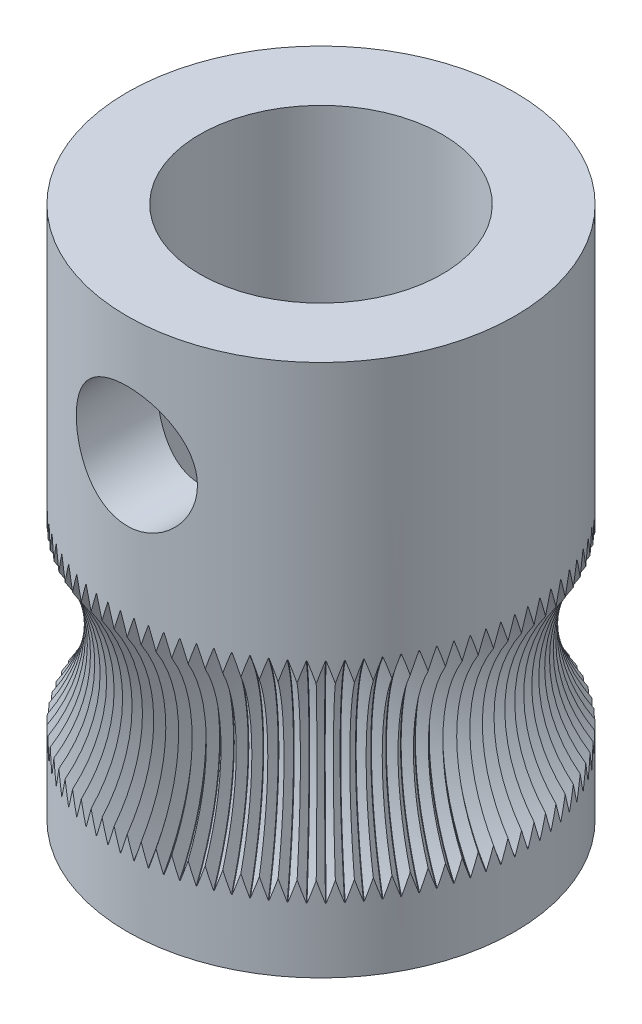
SolidWorks part; units mm, degrees
ref_plane "Front Plane" through (0, 0, 0) normal (0, 0, 1) x (1, 0, 0)
ref_plane "Top Plane" through (0, 0, 0) normal (0, 1, 0) x (1, 0, 0)
ref_plane "Right Plane" through (0, 0, 0) normal (1, 0, 0) x (0, 0, -1)
sketch "Sketch1" plane through (0, 0, 0) normal (0, 1, 0) x (1, 0, 0)
  circle A0 centre (0, 0) radius 4
  circle A1 centre (0, 0) radius 2.5
  dimension "D1" = 8
  dimension "D2" = 5
extrude "Boss-Extrude1" add sketch "Sketch1" along normal blind 11
ref_plane "Plane1" through (0, 0, 4) normal (0, 0, 1) x (1, 0, 0)
ref_axis "Axis1" through (0, 11, 0) along (0, -1, 0)
hole_wizard "M3 Tapped Hole1" positions "Sketch6" profile "Sketch7" tap size "M3" standard "ISO" end condition up to next
sketch "Sketch6" plane through (0, 0, 4) normal (0, 0, 1) x (1, 0, 0)
  line L0 (4, 11) -> (-4, 11) construction
  line L1 (0, 11) -> (0, 0) construction
  point P1 (0, 8.5)
  dimension "D1" = 2.5
cosmetic thread "Hole Thread1" parameters "D2"=3
sketch "Sketch7" plane through (0, 8.5, 4) normal (1, 0, 0) x (0, -1, 0)
  line L0 (0, 0) -> (0, 1.5)
  line L1 (0, 1.5) -> (1.25, 1.5)
  line L2 (1.25, 1.5) -> (1.25, 0)
  line L5 (1.25, 0) -> (0, 0)
  line L11 (0, -6.35) -> (0, 107.95) construction
  dimension "Thru Tap Drill Dia." = 2.5
  dimension "Thru Tap Drill Depth" = 1.5
ref_plane "Plane3" through (0, 0, 0) normal (0, 0, 1) x (1, 0, 0)
sketch "Sketch8" plane through (0, 0, 0) normal (0, 0, 1) x (1, 0, 0)
  line L0 (0, 11) -> (0, 0) construction
  line L1 (4, 11) -> (-4, 11) construction
  line L2 (6.75, 3.5) -> (6.75, 8.3641) construction
  circle A0 centre (6.75, 3.5) radius 3.5
  point P6 (6.75, 7)
  dimension "D1" = 7
  dimension "D2" = 6.75
  dimension "D3" = 7.5
ref_plane "Plane4" through (6.75, 0, 0) normal (1, 0, 0) x (0, 0, -1)
sketch "Sketch10" plane through (6.75, 0, 0) normal (1, 0, 0) x (0, 0, -1)
  line L0 (-0.9697, 5.3292) -> (0.9697, 5.3292)
  line L1 (0.9697, 5.3292) -> (0.005, 7)
  line L2 (0.005, 7) -> (-0.005, 7)
  line L3 (-0.005, 7) -> (-0.9697, 5.3292)
  line L6 (0, 3.5) -> (0, 8.3641) construction
  point P2 (0, 7)
  point P5 (0, 5.3292)
  dimension "D1" = 0.01
  dimension "D2" = 60
sweep "Cut-Sweep1" cut profiles "Sketch10" path "Sketch8"
pattern_circular "CirPattern1" count 90 every 4 about axis through (0, 11, 0) along (0, -1, 0) of "Cut-Sweep1"
